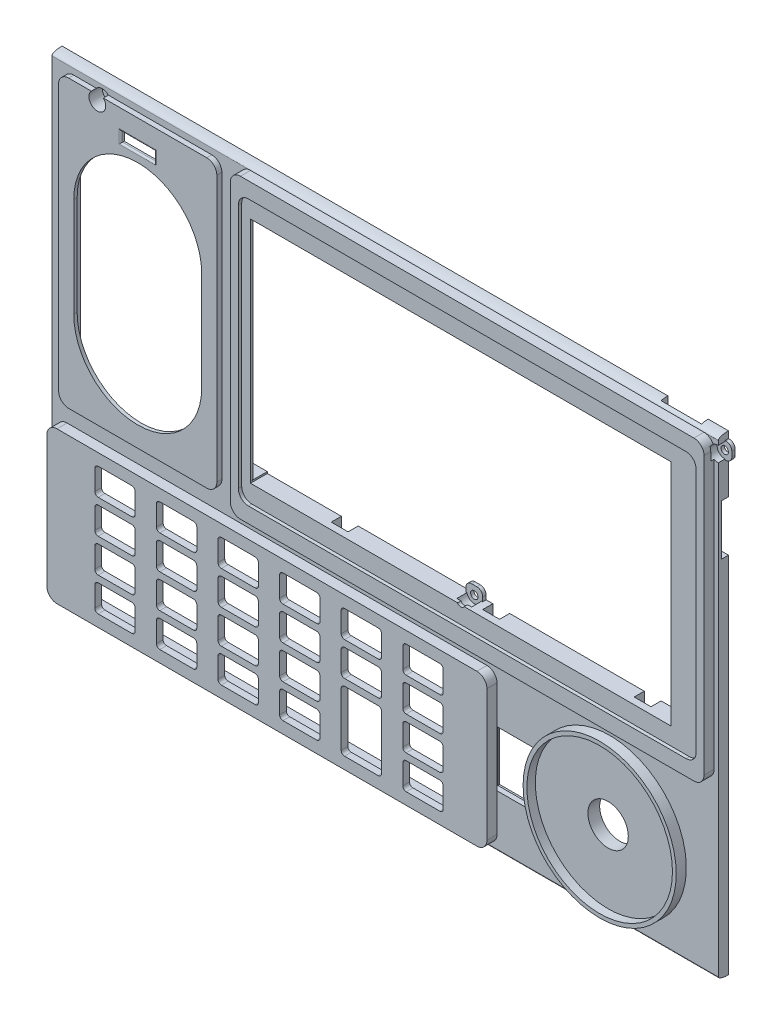
SolidWorks part; units mm, degrees
ref_plane "Front Plane" through (0, 0, 0) normal (0, 0, 1) x (1, 0, 0)
ref_plane "Top Plane" through (0, 0, 0) normal (0, 1, 0) x (1, 0, 0)
ref_plane "Right Plane" through (0, 0, 0) normal (1, 0, 0) x (0, 0, -1)
sketch "Sketch1" plane through (0, 0, 0) normal (0, 0, 1) x (1, 0, 0)
  line L1 (99, -70) -> (-99, -70)
  line L2 (99, -70) -> (99, 70)
  line L3 (99, 70) -> (-99, 70)
  line L4 (-99, -70) -> (-99, 70)
  line L5 (99, -70) -> (-99, 70) construction
  line L6 (99, 70) -> (-99, -70) construction
  point P0 (0, 0)
  dimension "D1" = 198
  dimension "D2" = 140
extrude "main_body" add sketch "Sketch1" along normal blind 3
fillet "long_corners" radius 3 2 edges at (0, 70, 3) (0, -70, 3) second distance 1 first distance on face at (0, 70, 1.5) first distance on face at (0, -70, 1.5)
sketch "Sketch2" plane through (0, 0, 3) normal (0, 0, 1) x (1, 0, 0)
  line L0 (-99, 24.75) -> (99, 24.75) construction
  line L1 (-99, 69) -> (-99, -69) construction
  line L2 (99, -69) -> (99, 69) construction
  line L3 (99, 69) -> (-99, 69) construction
  line L4 (-48.5, -17.75) -> (-95.5, -17.75)
  line L5 (-48.5, -17.75) -> (-48.5, 67.25)
  line L6 (-48.5, 67.25) -> (-95.5, 67.25)
  line L7 (-95.5, -17.75) -> (-95.5, 67.25)
  line L8 (-48.5, -17.75) -> (-95.5, 67.25) construction
  line L9 (-48.5, 67.25) -> (-95.5, -17.75) construction
  point P6 (-72, 24.75)
  dimension "D1" = 85
  dimension "D2" = 47
  dimension "D3" = 27
  dimension "D4" = 44.25
extrude "speaker" add sketch "Sketch2" along normal blind 1.5
fillet "speaker_corners" radius 3 4 edges at (-95.5, 67.25, 3.75) (-95.5, -17.75, 3.75) (-48.5, -17.75, 3.75) (-48.5, 67.25, 3.75)
sketch "Sketch19" plane through (0, 0, 4.5) normal (0, 0, 1) x (1, 0, 0)
  line L0 (-72, 67.25) -> (-72, -17.75) construction
  line L1 (-51.5, 67.25) -> (-92.5, 67.25) construction
  line L2 (-92.5, -17.75) -> (-51.5, -17.75) construction
  line L3 (-72, 7.25) -> (-72, 36.75) construction
  line L4 (-95.5, 64.25) -> (-95.5, -14.75) construction
  line L5 (-95.5, 24.75) -> (-48.5, 24.75) construction
  line L6 (-48.5, -14.75) -> (-48.5, 64.25) construction
  line L7 (-91, 7.25) -> (-91, 36.75)
  line L8 (-53, 7.25) -> (-53, 36.75)
  arc A0 (-91, 7.25) -> (-53, 7.25) centre (-72, 7.25) ccw
  arc A1 (-53, 36.75) -> (-91, 36.75) centre (-72, 36.75) ccw
  point P14 (-72, 22)
  point P19 (-72, -11.75)
  point P20 (-72, 55.75)
  dimension "D2" = 67.5
  dimension "D1" = 38
  dimension "D3" = 11.5
  dimension "D4" = 6
extrude "speaker_cut" cut sketch "Sketch19" against normal through all
sketch "Sketch21" plane through (0, 0, 0) normal (0, 0, -1) x (-1, 0, 0)
  line L0 (72, -11.75) -> (72, 55.75) construction
  line L2 (53, 7.25) -> (53, 36.75) construction
  line L3 (53, 22) -> (91, 22) construction
  line L4 (91, 36.75) -> (91, 7.25) construction
  line L5 (50.5, 61) -> (93.5, 61)
  line L6 (50.5, 61) -> (50.5, -17)
  line L7 (50.5, -17) -> (93.5, -17)
  line L8 (93.5, 61) -> (93.5, -17)
  line L9 (50.5, 61) -> (93.5, -17) construction
  line L10 (50.5, -17) -> (93.5, 61) construction
  arc A0 (53, 7.25) -> (91, 7.25) centre (72, 7.25) ccw construction
  arc A1 (91, 36.75) -> (53, 36.75) centre (72, 36.75) ccw construction
  point P14 (72, 22)
  dimension "D1" = 43
  dimension "D2" = 78
extrude "speaker_slot" cut sketch "Sketch21" against normal blind 3.5
sketch "Sketch3" plane through (0, 0, 3) normal (0, 0, 1) x (1, 0, 0)
  line L0 (-99, 24.875) -> (99, 24.875) construction
  line L1 (-99, 69) -> (-99, -69) construction
  line L2 (99, -69) -> (99, 69) construction
  line L4 (-48.5, -14.75) -> (-48.5, 64.25) construction
  line L5 (97.75, -19.25) -> (-43, -19.25)
  line L6 (97.75, -19.25) -> (97.75, 69)
  line L7 (97.75, 69) -> (-43, 69)
  line L8 (-43, -19.25) -> (-43, 69)
  line L9 (97.75, -19.25) -> (-43, 69) construction
  line L10 (97.75, 69) -> (-43, -19.25) construction
  line L11 (99, 70) -> (-99, 70) construction
  point P8 (27.375, 24.875)
  dimension "D1" = 1
  dimension "D2" = 88.25
  dimension "D3" = 140.75
  dimension "D4" = 1.25
  dimension "D5" = 5.5
extrude "lcd" add sketch "Sketch3" along normal blind 3
fillet "lcd_corners" radius 3 4 edges at (97.75, -19.25, 4.5) (-43, -19.25, 4.5)
sketch "Sketch9" plane through (0, 0, 6) normal (0, 0, 1) x (1, 0, 0)
  line L0 (-43, 24.85) -> (97.75, 24.85) construction
  line L1 (-43, 66) -> (-43, -16.25) construction
  line L2 (97.75, -16.25) -> (97.75, 66) construction
  line L3 (-40, -19.25) -> (94.75, -19.25) construction
  line L4 (95.4, -14.65) -> (-40.6, -14.65)
  line L5 (95.4, -14.65) -> (95.4, 64.35)
  line L6 (95.4, 64.35) -> (-40.6, 64.35)
  line L7 (-40.6, -14.65) -> (-40.6, 64.35)
  line L8 (95.4, -14.65) -> (-40.6, 64.35) construction
  line L9 (95.4, 64.35) -> (-40.6, -14.65) construction
  line L10 (94.75, 69) -> (-40, 69) construction
  line L11 (97.75, -16.25) -> (97.75, 66) construction
  point P6 (27.4, 24.85)
  dimension "D1" = 136
  dimension "D2" = 79
  dimension "D3" = 2.4
  dimension "D4" = 4.6
  dimension "D5" = 4.65
  dimension "D6" = 2.35
extrude "lcd_front" cut sketch "Sketch9" against normal blind 1
fillet "lcd_front_corners" radius 3 4 edges at (95.4, -14.65, 5.5) (95.4, 64.35, 5.5) (-40.6, 64.35, 5.5) (-40.6, -14.65, 5.5)
sketch "Sketch10" plane through (0, 0, 0) normal (0, 0, -1) x (-1, 0, 0)
  line L0 (-95.4, -11.65) -> (-95.4, 61.35) construction
  line L1 (-92.4, 64.35) -> (37.6, 64.35) construction
  line L2 (40.6, 64.35) -> (40.6, -14.65) construction
  line L3 (-95.4, 64.35) -> (40.6, 64.35) construction
  line L4 (38, -9.5) -> (-87, -9.5)
  line L5 (38, -9.5) -> (38, 58.5)
  line L6 (38, 58.5) -> (-87, 58.5)
  line L7 (-87, -9.5) -> (-87, 58.5)
  line L8 (-87, -9.5) -> (38, 58.5) construction
  line L9 (-87, 58.5) -> (38, -9.5) construction
  line L10 (-99, -70) -> (-99, 70) construction
  line L11 (-99, 70) -> (99, 70) construction
  line L13 (37.6, -14.65) -> (-92.4, -14.65) construction
  dimension "D1" = 125
  dimension "D2" = 68
  dimension "D3" = 12
  dimension "D4" = 2.6
  dimension "D5" = 11.5
  dimension "D6" = 5.85
  dimension "D7" = 8.4
  dimension "D8" = 5.85
  dimension "D9" = 5.15
extrude "lcd_back" cut sketch "Sketch10" against normal through all
sketch "Sketch56" plane through (0, 0, 0) normal (0, 0, -1) x (-1, 0, 0)
  line L0 (-87, -9.5) -> (38, -9.5) construction
  line L1 (-79, -9.5) -> (-74, -9.5)
  line L2 (-79, -9.5) -> (-79, -12.5)
  line L3 (-79, -12.5) -> (-74, -12.5)
  line L4 (-74, -9.5) -> (-74, -12.5)
  line L5 (38, 58.5) -> (-87, 58.5) construction
  line L6 (-34, -9.5) -> (-29, -9.5)
  line L7 (-34, -9.5) -> (-34, -12.5)
  line L8 (-34, -12.5) -> (-29, -12.5)
  line L9 (-29, -9.5) -> (-29, -12.5)
  line L10 (11, -9.5) -> (16, -9.5)
  line L11 (11, -9.5) -> (11, -12.5)
  line L12 (11, -12.5) -> (16, -12.5)
  line L13 (16, -9.5) -> (16, -12.5)
  line L14 (-79, 58.5) -> (-74, 58.5)
  line L15 (-79, 58.5) -> (-79, 61.5)
  line L16 (-79, 61.5) -> (-74, 61.5)
  line L17 (-74, 58.5) -> (-74, 61.5)
  line L18 (38, -9.5) -> (38, 58.5) construction
  line L19 (-34, 58.5) -> (-29, 58.5)
  line L20 (-34, 58.5) -> (-34, 61.5)
  line L21 (-34, 61.5) -> (-29, 61.5)
  line L22 (-29, 58.5) -> (-29, 61.5)
  line L23 (11, 58.5) -> (16, 58.5)
  line L24 (11, 58.5) -> (11, 61.5)
  line L25 (11, 61.5) -> (16, 61.5)
  line L26 (16, 58.5) -> (16, 61.5)
  line L27 (38, 58) -> (42, 58)
  line L28 (38, 58) -> (38, -9)
  line L29 (38, -9) -> (42, -9)
  line L30 (42, 58) -> (42, -9)
  line L31 (-99, -70) -> (-99, 70) construction
  line L32 (-99, 70) -> (99, 70) construction
  point P34 (-29, -11)
  dimension "D1" = 5
  dimension "D2" = 5
  dimension "D3" = 5
  dimension "D4" = 5
  dimension "D5" = 5
  dimension "D6" = 5
  dimension "D7" = 67
  dimension "D8" = 4
  dimension "D9" = 3
  dimension "D10" = 3
  dimension "D11" = 3
  dimension "D12" = 3
  dimension "D13" = 3
  dimension "D14" = 3
  dimension "D15" = 40
  dimension "D16" = 40
  dimension "D17" = 20
  dimension "D18" = 20
  dimension "D19" = 40
  dimension "D20" = 40
  dimension "D21" = 12
extrude "lcd_glue_points" cut sketch "Sketch56" against normal blind 3
sketch "Sketch4" plane through (0, 0, 3) normal (0, 0, 1) x (1, 0, 0)
  line L0 (-99, -45.75) -> (99, -45.75) construction
  line L1 (-99, 69) -> (-99, -69) construction
  line L2 (99, -69) -> (99, 69) construction
  line L4 (-92.5, -17.75) -> (-51.5, -17.75) construction
  line L5 (33.25, -68.25) -> (-97.5, -68.25)
  line L6 (33.25, -68.25) -> (33.25, -23.25)
  line L7 (33.25, -23.25) -> (-97.5, -23.25)
  line L8 (-97.5, -68.25) -> (-97.5, -23.25)
  line L9 (33.25, -68.25) -> (-97.5, -23.25) construction
  line L10 (33.25, -23.25) -> (-97.5, -68.25) construction
  line L11 (-99, -70) -> (99, -70) construction
  point P8 (-32.125, -45.75)
  dimension "D1" = 1.75
  dimension "D2" = 130.75
  dimension "D3" = 45
  dimension "D4" = 1.5
  dimension "D5" = 5.5
extrude "keypad" add sketch "Sketch4" along normal blind 3
fillet "keypad_corners" radius 3 4 edges at (-97.5, -68.25, 4.5) (33.25, -68.25, 4.5) (33.25, -23.25, 4.5) (-97.5, -23.25, 4.5)
sketch "Sketch25" plane through (0, 0, 6) normal (0, 0, 1) x (1, 0, 0)
  line L0 (-97.5, -30.75) -> (33.25, -30.75) construction
  line L1 (30.25, -23.25) -> (-94.5, -23.25) construction
  line L2 (-94.5, -68.25) -> (30.25, -68.25) construction
  line L3 (-77.25, -23.25) -> (-77.25, -68.25) construction
  line L5 (-34.65, -64.75) -> (33.25, -64.75) construction
  line L6 (-97.5, -26.25) -> (-97.5, -65.25) construction
  line L11 (33.25, -65.25) -> (33.25, -26.25) construction
  line L12 (-58.95, -23.25) -> (-58.95, -68.25) construction
  line L13 (-97.5, -40.75) -> (33.25, -40.75) construction
  line L14 (30.25, -23.25) -> (-94.5, -23.25) construction
  line L15 (-40.65, -23.25) -> (-40.65, -68.25) construction
  line L16 (-94.5, -68.25) -> (30.25, -68.25) construction
  line L17 (-71.25, -34.75) -> (-83.25, -34.75)
  line L18 (-22.35, -23.25) -> (-22.35, -68.25) construction
  line L19 (-97.5, -50.75) -> (33.25, -50.75) construction
  line L20 (-4.05, -23.25) -> (-4.05, -68.25) construction
  line L21 (-71.25, -34.75) -> (-71.25, -26.75)
  line L22 (14.25, -23.25) -> (14.25, -68.25) construction
  line L23 (-97.5, -26.25) -> (-97.5, -65.25) construction
  line L24 (-97.5, -60.75) -> (33.25, -60.75) construction
  line L25 (-71.25, -26.75) -> (-83.25, -26.75)
  line L26 (-83.25, -34.75) -> (-83.25, -26.75)
  line L27 (-71.25, -34.75) -> (-83.25, -26.75) construction
  line L28 (-71.25, -26.75) -> (-83.25, -34.75) construction
  line L29 (-71.25, -44.75) -> (-83.25, -44.75)
  line L30 (-71.25, -44.75) -> (-71.25, -36.75)
  line L31 (-71.25, -36.75) -> (-83.25, -36.75)
  line L32 (-83.25, -44.75) -> (-83.25, -36.75)
  line L33 (-71.25, -44.75) -> (-83.25, -36.75) construction
  line L34 (-71.25, -36.75) -> (-83.25, -44.75) construction
  line L35 (-71.25, -54.75) -> (-83.25, -54.75)
  line L36 (-71.25, -54.75) -> (-71.25, -46.75)
  line L37 (-71.25, -46.75) -> (-83.25, -46.75)
  line L38 (-83.25, -54.75) -> (-83.25, -46.75)
  line L39 (-71.25, -54.75) -> (-83.25, -46.75) construction
  line L40 (-71.25, -46.75) -> (-83.25, -54.75) construction
  line L41 (-71.25, -64.75) -> (-83.25, -64.75)
  line L42 (-71.25, -64.75) -> (-71.25, -56.75)
  line L43 (-71.25, -56.75) -> (-83.25, -56.75)
  line L44 (-83.25, -64.75) -> (-83.25, -56.75)
  line L45 (-71.25, -64.75) -> (-83.25, -56.75) construction
  line L46 (-71.25, -56.75) -> (-83.25, -64.75) construction
  line L47 (-52.95, -34.75) -> (-64.95, -34.75)
  line L48 (-52.95, -34.75) -> (-52.95, -26.75)
  line L49 (-52.95, -26.75) -> (-64.95, -26.75)
  line L50 (-64.95, -34.75) -> (-64.95, -26.75)
  line L51 (-52.95, -34.75) -> (-64.95, -26.75) construction
  line L52 (-52.95, -26.75) -> (-64.95, -34.75) construction
  line L53 (-52.95, -44.75) -> (-64.95, -44.75)
  line L54 (-52.95, -44.75) -> (-52.95, -36.75)
  line L55 (-52.95, -36.75) -> (-64.95, -36.75)
  line L56 (-64.95, -44.75) -> (-64.95, -36.75)
  line L57 (-52.95, -44.75) -> (-64.95, -36.75) construction
  line L58 (-52.95, -36.75) -> (-64.95, -44.75) construction
  line L59 (-52.95, -54.75) -> (-64.95, -54.75)
  line L60 (-52.95, -54.75) -> (-52.95, -46.75)
  line L61 (-52.95, -46.75) -> (-64.95, -46.75)
  line L62 (-64.95, -54.75) -> (-64.95, -46.75)
  line L63 (-52.95, -54.75) -> (-64.95, -46.75) construction
  line L64 (-52.95, -46.75) -> (-64.95, -54.75) construction
  line L65 (-52.95, -64.75) -> (-64.95, -64.75)
  line L66 (-52.95, -64.75) -> (-52.95, -56.75)
  line L67 (-52.95, -56.75) -> (-64.95, -56.75)
  line L68 (-64.95, -64.75) -> (-64.95, -56.75)
  line L69 (-52.95, -64.75) -> (-64.95, -56.75) construction
  line L70 (-52.95, -56.75) -> (-64.95, -64.75) construction
  line L71 (-34.65, -34.75) -> (-46.65, -34.75)
  line L72 (-34.65, -34.75) -> (-34.65, -26.75)
  line L73 (-34.65, -26.75) -> (-46.65, -26.75)
  line L74 (-46.65, -34.75) -> (-46.65, -26.75)
  line L75 (-34.65, -34.75) -> (-46.65, -26.75) construction
  line L76 (-34.65, -26.75) -> (-46.65, -34.75) construction
  line L77 (-34.65, -44.75) -> (-46.65, -44.75)
  line L78 (-34.65, -44.75) -> (-34.65, -36.75)
  line L79 (-34.65, -36.75) -> (-46.65, -36.75)
  line L80 (-46.65, -44.75) -> (-46.65, -36.75)
  line L81 (-34.65, -44.75) -> (-46.65, -36.75) construction
  line L82 (-34.65, -36.75) -> (-46.65, -44.75) construction
  line L83 (-34.65, -54.75) -> (-46.65, -54.75)
  line L84 (-34.65, -54.75) -> (-34.65, -46.75)
  line L85 (-34.65, -46.75) -> (-46.65, -46.75)
  line L86 (-46.65, -54.75) -> (-46.65, -46.75)
  line L87 (-34.65, -54.75) -> (-46.65, -46.75) construction
  line L88 (-34.65, -46.75) -> (-46.65, -54.75) construction
  line L89 (-34.65, -64.75) -> (-46.65, -64.75)
  line L90 (-34.65, -64.75) -> (-34.65, -56.75)
  line L91 (-34.65, -56.75) -> (-46.65, -56.75)
  line L92 (-46.65, -64.75) -> (-46.65, -56.75)
  line L93 (-34.65, -64.75) -> (-46.65, -56.75) construction
  line L94 (-34.65, -56.75) -> (-46.65, -64.75) construction
  line L95 (-16.35, -34.75) -> (-28.35, -34.75)
  line L96 (-16.35, -34.75) -> (-16.35, -26.75)
  line L97 (-16.35, -26.75) -> (-28.35, -26.75)
  line L98 (-28.35, -34.75) -> (-28.35, -26.75)
  line L99 (-16.35, -34.75) -> (-28.35, -26.75) construction
  line L100 (-16.35, -26.75) -> (-28.35, -34.75) construction
  line L101 (-16.35, -44.75) -> (-28.35, -44.75)
  line L102 (-16.35, -44.75) -> (-16.35, -36.75)
  line L103 (-16.35, -36.75) -> (-28.35, -36.75)
  line L104 (-28.35, -44.75) -> (-28.35, -36.75)
  line L105 (-16.35, -44.75) -> (-28.35, -36.75) construction
  line L106 (-16.35, -36.75) -> (-28.35, -44.75) construction
  line L111 (-16.35, -54.75) -> (-28.35, -54.75)
  line L112 (-16.35, -54.75) -> (-16.35, -46.75)
  line L113 (-16.35, -46.75) -> (-28.35, -46.75)
  line L114 (-28.35, -54.75) -> (-28.35, -46.75)
  line L115 (-16.35, -54.75) -> (-28.35, -46.75) construction
  line L116 (-16.35, -46.75) -> (-28.35, -54.75) construction
  line L117 (-16.35, -64.75) -> (-28.35, -64.75)
  line L118 (-16.35, -64.75) -> (-16.35, -56.75)
  line L119 (-16.35, -56.75) -> (-28.35, -56.75)
  line L120 (-28.35, -64.75) -> (-28.35, -56.75)
  line L121 (-16.35, -64.75) -> (-28.35, -56.75) construction
  line L122 (-16.35, -56.75) -> (-28.35, -64.75) construction
  line L127 (1.95, -34.75) -> (-10.05, -34.75)
  line L128 (1.95, -34.75) -> (1.95, -26.75)
  line L129 (1.95, -26.75) -> (-10.05, -26.75)
  line L130 (-10.05, -34.75) -> (-10.05, -26.75)
  line L131 (1.95, -34.75) -> (-10.05, -26.75) construction
  line L132 (1.95, -26.75) -> (-10.05, -34.75) construction
  line L133 (20.25, -34.75) -> (8.25, -34.75)
  line L134 (20.25, -34.75) -> (20.25, -26.75)
  line L135 (20.25, -26.75) -> (8.25, -26.75)
  line L136 (8.25, -34.75) -> (8.25, -26.75)
  line L137 (20.25, -34.75) -> (8.25, -26.75) construction
  line L138 (20.25, -26.75) -> (8.25, -34.75) construction
  line L139 (1.95, -44.75) -> (-10.05, -44.75)
  line L140 (1.95, -44.75) -> (1.95, -36.75)
  line L141 (1.95, -36.75) -> (-10.05, -36.75)
  line L142 (-10.05, -44.75) -> (-10.05, -36.75)
  line L143 (1.95, -44.75) -> (-10.05, -36.75) construction
  line L144 (1.95, -36.75) -> (-10.05, -44.75) construction
  line L145 (20.25, -44.75) -> (8.25, -44.75)
  line L146 (20.25, -44.75) -> (20.25, -36.75)
  line L147 (20.25, -36.75) -> (8.25, -36.75)
  line L148 (8.25, -44.75) -> (8.25, -36.75)
  line L149 (20.25, -44.75) -> (8.25, -36.75) construction
  line L150 (20.25, -36.75) -> (8.25, -44.75) construction
  line L151 (20.25, -54.75) -> (8.25, -54.75)
  line L152 (20.25, -54.75) -> (20.25, -46.75)
  line L153 (20.25, -46.75) -> (8.25, -46.75)
  line L154 (8.25, -54.75) -> (8.25, -46.75)
  line L155 (20.25, -54.75) -> (8.25, -46.75) construction
  line L156 (20.25, -46.75) -> (8.25, -54.75) construction
  line L157 (20.25, -64.75) -> (8.25, -64.75)
  line L158 (20.25, -64.75) -> (20.25, -56.75)
  line L159 (20.25, -56.75) -> (8.25, -56.75)
  line L160 (8.25, -64.75) -> (8.25, -56.75)
  line L161 (20.25, -64.75) -> (8.25, -56.75) construction
  line L162 (20.25, -56.75) -> (8.25, -64.75) construction
  line L163 (1.95, -64.75) -> (-10.05, -64.75)
  line L164 (1.95, -64.75) -> (1.95, -46.75)
  line L165 (1.95, -46.75) -> (-10.05, -46.75)
  line L166 (-10.05, -64.75) -> (-10.05, -46.75)
  line L167 (1.95, -64.75) -> (-10.05, -46.75) construction
  line L168 (1.95, -46.75) -> (-10.05, -64.75) construction
  point P34 (-77.25, -30.75)
  point P39 (-77.25, -40.75)
  point P44 (-77.25, -50.75)
  point P49 (-77.25, -60.75)
  point P54 (-58.95, -30.75)
  point P59 (-58.95, -40.75)
  point P64 (-58.95, -50.75)
  point P69 (-58.95, -60.75)
  point P74 (-40.65, -30.75)
  point P79 (-40.65, -40.75)
  point P84 (-40.65, -50.75)
  point P89 (-40.65, -60.75)
  point P94 (-22.35, -30.75)
  point P99 (-22.35, -40.75)
  point P104 (-22.35, -50.75)
  point P109 (-22.35, -60.75)
  point P114 (-4.05, -30.75)
  point P119 (14.25, -30.75)
  point P124 (-4.05, -40.75)
  point P129 (14.25, -40.75)
  point P134 (14.25, -50.75)
  point P139 (14.25, -60.75)
  point P144 (-4.05, -55.75)
  dimension "D1" = 19
  dimension "D2" = 18.3
  dimension "D3" = 18.3
  dimension "D4" = 18.3
  dimension "D5" = 18.3
  dimension "D6" = 18.3
  dimension "D7" = 20.25
  dimension "D8" = 7.5
  dimension "D9" = 10
  dimension "D10" = 10
  dimension "D11" = 10
  dimension "D12" = 7.5
  dimension "D13" = 12
  dimension "D14" = 12
  dimension "D15" = 12
  dimension "D16" = 12
  dimension "D17" = 12
  dimension "D18" = 12
  dimension "D19" = 12
  dimension "D20" = 12
  dimension "D21" = 12
  dimension "D22" = 12
  dimension "D23" = 12
  dimension "D24" = 12
  dimension "D25" = 12
  dimension "D26" = 12
  dimension "D27" = 12
  dimension "D28" = 12
  dimension "D29" = 12
  dimension "D30" = 12
  dimension "D31" = 12
  dimension "D32" = 12
  dimension "D33" = 12
  dimension "D34" = 12
  dimension "D35" = 12
  dimension "D36" = 8
  dimension "D37" = 8
  dimension "D38" = 8
  dimension "D39" = 8
  dimension "D40" = 8
  dimension "D41" = 8
  dimension "D42" = 18
  dimension "D43" = 8
  dimension "D44" = 8
  dimension "D45" = 8
  dimension "D46" = 8
  dimension "D47" = 8
  dimension "D48" = 8
  dimension "D49" = 8
  dimension "D50" = 8
  dimension "D51" = 8
  dimension "D52" = 8
  dimension "D53" = 8
  dimension "D54" = 8
  dimension "D55" = 8
  dimension "D56" = 8
  dimension "D57" = 8
  dimension "D58" = 8
  dimension "D59" = 5
extrude "keypad_cuts_0.8" cut sketch "Sketch25" against normal through all
sketch "Sketch5" plane through (0, 0, 3) normal (0, 0, 1) x (1, 0, 0)
  line L0 (33.25, -45.75) -> (99, -45.75) construction
  line L1 (33.25, -65.25) -> (33.25, -26.25) construction
  line L2 (99, -69) -> (99, 69) construction
  circle A0 centre (66.75, -45.75) radius 22.75
  dimension "D1" = 45.5
  dimension "D2" = 32.25
  dimension "D3" = 33.5
extrude "vfo" add sketch "Sketch5" along normal blind 3
sketch "Sketch7" plane through (0, 0, 6) normal (0, 0, 1) x (1, 0, 0)
  line L0 (44, -45.75) -> (89.5, -45.75) construction
  line L1 (66.75, -23) -> (66.75, -68.5) construction
  circle A0 centre (66.75, -45.75) radius 22.75 construction
  circle A1 centre (66.75, -45.75) radius 22.75 construction
  circle A2 centre (66.75, -45.75) radius 6
  dimension "D1" = 12
extrude "vfo_encoder_knob_cut" cut sketch "Sketch7" against normal through all
sketch "esp32" plane through (0, 0, 0) normal (0, 0, -1) x (-1, 0, 0)
  line L0 (99, -70) -> (-99, -70) construction
  line L1 (-50.5, -37.5) -> (-32, -37.5)
  line L2 (-50.5, -37.5) -> (-50.5, -54)
  line L3 (-50.5, -54) -> (-32, -54)
  line L4 (-32, -37.5) -> (-32, -54)
  line L5 (-99, -70) -> (-99, 70) construction
  dimension "D1" = 16
  dimension "D2" = 48.5
  dimension "D3" = 16.5
  dimension "D4" = 18.5
extrude "esp32_can_cut" cut sketch "esp32" against normal blind 3
sketch "Sketch47" plane through (0, 0, 0) normal (0, 0, -1) x (-1, 0, 0)
  line L0 (-50.5, -54) -> (-32, -54) construction
  line L1 (-31, -55) -> (-58, -55)
  line L2 (-31, -55) -> (-31, -36.5)
  line L3 (-31, -36.5) -> (-58, -36.5)
  line L4 (-58, -55) -> (-58, -36.5)
  line L5 (-31, -55) -> (-58, -36.5) construction
  line L6 (-31, -36.5) -> (-58, -55) construction
  line L7 (-50.5, -37.5) -> (-50.5, -54) construction
  point P0 (-44.5, -45.75)
  dimension "D1" = 27
  dimension "D2" = 18.5
  dimension "D3" = 1
  dimension "D4" = 7.5
extrude "esp32_ex_cut" cut sketch "Sketch47" against normal blind 1.5
sketch "Sketch49" plane through (0, 0, 0) normal (0, 0, -1) x (-1, 0, 0)
  line L0 (72, 59.75) -> (72, 67.25) construction
  line L3 (51.5, 67.25) -> (92.5, 67.25) construction
  line L4 (77, 58.25) -> (67, 58.25)
  line L5 (77, 58.25) -> (77, 61.25)
  line L6 (77, 61.25) -> (67, 61.25)
  line L7 (67, 58.25) -> (67, 61.25)
  line L8 (77, 58.25) -> (67, 61.25) construction
  line L9 (77, 61.25) -> (67, 58.25) construction
  point P6 (72, 59.75)
  dimension "D1" = 10
  dimension "D2" = 3
  dimension "D3" = 7.5
extrude "amb_sensor" cut sketch "Sketch49" against normal through all
fillet "amb_corners" radius 0.5 4 edges at (-67, 59.75, 4.5) (-72, 61.25, 4.5) (-77, 59.75, 4.5) (-72, 58.25, 4.5)
sketch "Sketch55" plane through (0, 0, 0) normal (0, 0, -1) x (-1, 0, 0)
  line L0 (-99, -70) -> (-99, 70) construction
  line L5 (-93, 70) -> (-81, 70)
  line L6 (-93, 70) -> (-93, 58.5)
  line L11 (-93, 58.5) -> (-81, 58.5)
  line L12 (-81, 70) -> (-81, 58.5)
  line L13 (94.5, 48) -> (99, 48)
  line L14 (94.5, 48) -> (94.5, 33)
  line L15 (94.5, 33) -> (99, 33)
  line L16 (99, 48) -> (99, 33)
  line L17 (94.5, 48) -> (99, 33) construction
  line L18 (94.5, 33) -> (99, 48) construction
  line L23 (99, 65.5) -> (-99, 65.5) construction
  line L24 (99, -8.5) -> (-99, -8.5) construction
  line L35 (-99, -68) -> (99, -68) construction
  line L36 (99, -70) -> (-99, -70) construction
  line L42 (-99, 53) -> (-93, 53)
  line L43 (-99, 53) -> (-99, 38)
  line L44 (-99, 70) -> (99, 70) construction
  line L45 (-99, 38) -> (-93, 38)
  line L46 (99, 70) -> (99, -70) construction
  line L47 (-93, 53) -> (-93, 38)
  circle A1 centre (49.5, 65.5) radius 3
  circle A2 centre (-24.5, 65.5) radius 3
  circle A4 centre (49.5, -8.5) radius 3
  circle A6 centre (-68, -68) radius 3
  circle A7 centre (-1, -68) radius 3
  circle A9 centre (-32, 65.5) radius 3
  point P10 (96.75, 40.5)
  dimension "D8" = 6
  dimension "D9" = 6
  dimension "D13" = 6
  dimension "D18" = 2
  dimension "D19" = 6
  dimension "D21" = 6
  dimension "D22" = 6
  dimension "D1" = 12
  dimension "D3" = 11.5
  dimension "D4" = 0
  dimension "D5" = 6
  dimension "D6" = 4.5
  dimension "D11" = 49.5
  dimension "D12" = 123.5
  dimension "D14" = 7.5
  dimension "D15" = 61.5
  dimension "D24" = 100
  dimension "D25" = 15
  dimension "D26" = 4.5
  dimension "D27" = 0
  dimension "D28" = 22
  dimension "D29" = 49.5
  dimension "D30" = 67
  dimension "D31" = 6
  dimension "D32" = 15
  dimension "D33" = 0
  dimension "D34" = 17
extrude "conn_cutouts" cut sketch "Sketch55" against normal blind 2
fillet "Fillet1" radius 2 1 edges at (-38, 24.5, 3)
fillet "Fillet2" radius 5 1 edges at (-42, 24.5, 0)
sketch "Sketch57" plane through (0, 0, 0) normal (0, 0, -1) x (-1, 0, 0)
  line L0 (99, 70) -> (99, 48) construction
  line L1 (-24, -24.5) -> (89, -24.5)
  line L2 (-24, -24.5) -> (-24, -66.5)
  line L3 (-24, -66.5) -> (89, -66.5)
  line L4 (89, -24.5) -> (89, -66.5)
  line L5 (99, -70) -> (1.2361, -70) construction
  dimension "D1" = 113
  dimension "D2" = 42
  dimension "D3" = 10
  dimension "D4" = 3.5
extrude "keyboard_back" cut sketch "Sketch57" against normal blind 4
sketch "Sketch58" plane through (0, -9.5, 0) normal (0, 1, 0) x (1, 0, 0)
  line L1 (27, -1) -> (22, -1)
  line L2 (27, -1) -> (27, 0)
  line L3 (27, 0) -> (22, 0)
  line L4 (22, -1) -> (22, 0)
  line L5 (27, -1) -> (22, 0) construction
  line L6 (27, 0) -> (22, -1) construction
  line L7 (29, -3) -> (29, 0) construction
  line L9 (29, 0) -> (-11, 0) construction
  point P0 (24.5, -0.5)
  dimension "D1" = 1
  dimension "D2" = 5
  dimension "D3" = 2
  dimension "D4" = 0
extrude "behind_lcd_screew_mount" add sketch "Sketch58" along normal blind 3
sketch "Sketch59" plane through (-99, 0, 0) normal (-1, 0, 0) x (0, 0, 1)
  line L0 (0, 70) -> (0, 48) construction
  line L1 (0, -66.5) -> (1, -66.5)
  line L2 (0, -66.5) -> (0, -69.5)
  line L3 (0, -69.5) -> (1, -69.5)
  line L4 (1, -66.5) -> (1, -69.5)
  dimension "D1" = 1
  dimension "D2" = 3
  dimension "D3" = 66.5
extrude "keyb_screw_mount" add sketch "Sketch59" along normal blind 1
sketch "Sketch60" plane through (99, 0, 0) normal (1, 0, 0) x (0, 0, -1)
  line L0 (0, -70) -> (0, 38) construction
  line L1 (0, 68) -> (-1, 68)
  line L2 (0, 68) -> (0, 63)
  line L3 (0, 63) -> (-1, 63)
  line L4 (-1, 68) -> (-1, 63)
  dimension "D1" = 63
  dimension "D2" = 5
  dimension "D3" = 1
extrude "right_corner_screw_mount" add sketch "Sketch60" along normal blind 2
sketch "Sketch61" plane through (0, 0, 0) normal (0, 0, -1) x (-1, 0, 0)
  line L0 (-99, 70) -> (-93, 70) construction
  line L1 (-99, 68) -> (-99, 70) construction
  line L2 (-99, -9) -> (99, -9) construction
  line L3 (99, 70) -> (99, 48) construction
  line L5 (-99, -70) -> (-99, 38) construction
  line L6 (99, 70) -> (99, 48) construction
  line L7 (-3.2361, -70) -> (-65.7639, -70) construction
  line L8 (99, -69.5) -> (99, -70) construction
  line L9 (99, -70) -> (1.2361, -70) construction
  line L10 (-81, 70) -> (99, 70) construction
  circle A0 centre (-98.9, 65.5) radius 1.1
  circle A1 centre (-24.5, -9) radius 1.1
  circle A2 centre (98, -68) radius 1.1
  circle A3 centre (84, 65.5) radius 1.1
  dimension "D1" = 2.2
  dimension "D6" = 2.2
  dimension "D9" = 2.2
  dimension "D10" = 2.2
  dimension "D2" = 4.5
  dimension "D3" = 0.1
  dimension "D4" = 61
  dimension "D5" = 123.5
  dimension "D7" = 1
  dimension "D8" = 2
  dimension "D11" = 15
  dimension "D12" = 4.5
extrude "ui_screws" cut sketch "Sketch61" against normal through all
sketch "Sketch62" plane through (0, 0, 6) normal (0, 0, 1) x (1, 0, 0)
  line L0 (97.8, 65.5) -> (100, 65.5) construction
  line L1 (-98, -66.9) -> (-98, -69.1) construction
  line L2 (98.9, 66.6) -> (98.9, 64.4) construction
  line L4 (-96.9, -68) -> (-99.1, -68) construction
  circle A0 centre (24.5, -9) radius 2.25
  arc A1 (99, 66.5954) -> (99, 64.4046) centre (98.9, 65.5) ccw construction
  arc A2 (99, 64.4046) -> (99, 66.5954) centre (98.9, 65.5) ccw construction
  circle A3 centre (98.9, 65.5) radius 2.25
  arc A4 (-97.5417, -69) -> (-99, -67.5417) centre (-98, -68) ccw construction
  arc A5 (-98.4583, -69) -> (-97.5417, -69) centre (-98, -68) ccw construction
  arc A6 (-99, -67.5417) -> (-99, -68.4583) centre (-98, -68) ccw construction
  circle A7 centre (-98, -68) radius 2.25
  dimension "D1" = 4.5
  dimension "D2" = 4.5
  dimension "D3" = 4.5
extrude "ui_screw_head" cut sketch "Sketch62" against normal blind 3 from offset 2 offset against normal yes
fillet "ui_screw_mount_corners" radius 1.75 6 edges at (-100, -66.5, 0.5) (-100, -69.5, 0.5) (101, 63, 0.5) (101, 68, 0.5) (22, -6.5, 0.5) (27, -6.5, 0.5)
sketch "Sketch63" plane through (0, 0, 6) normal (0, 0, 1) x (1, 0, 0)
  circle A0 centre (66.75, -45.75) radius 21.625
  dimension "D1" = 43.25
extrude "enc_knob_slot" cut sketch "Sketch63" against normal blind 2.5
sketch "Sketch64" plane through (0, 0, 4.5) normal (0, 0, 1) x (1, 0, 0)
  circle A0 centre (-84, 65.5) radius 2.5
  dimension "D1" = 5
extrude "on_speaker_ui_screw_head" cut sketch "Sketch64" against normal blind 4
fillet "Fillet3" radius 2 4 edges at (-89, -66.5, 2) (-89, -24.5, 2) (24, -66.5, 2) (24, -24.5, 2)
fillet "Fillet4" radius 1 92 edges at (-83.25, -34.75, 5) (-71.25, -34.75, 5) (-71.25, -26.75, 5) (-83.25, -26.75, 5) (8.25, -64.75, 5) (20.25, -64.75, 5) (20.25, -56.75, 5) (8.25, -56.75, 5) (20.25, -54.75, 5) (8.25, -54.75, 5) (8.25, -46.75, 5) (20.25, -46.75, 5) (8.25, -44.75, 5) (20.25, -44.75, 5) (8.25, -36.75, 5) (20.25, -36.75, 5) (8.25, -34.75, 5) (20.25, -34.75, 5) (20.25, -26.75, 5) (8.25, -26.75, 5) (-10.05, -64.75, 5) (1.95, -64.75, 5) (-10.05, -46.75, 5) (1.95, -46.75, 5) (-10.05, -36.75, 5) (-10.05, -44.75, 5) (1.95, -44.75, 5) (1.95, -36.75, 5) (-10.05, -34.75, 5) (1.95, -34.75, 5) (-10.05, -26.75, 5) (1.95, -26.75, 5) (-28.35, -56.75, 5) (-28.35, -64.75, 5) (-16.35, -64.75, 5) (-16.35, -56.75, 5) (-28.35, -46.75, 5) (-28.35, -54.75, 5) (-16.35, -54.75, 5) (-16.35, -46.75, 5) (-28.35, -44.75, 5) (-16.35, -44.75, 5) (-16.35, -36.75, 5) (-28.35, -36.75, 5) (-28.35, -34.75, 5) (-16.35, -34.75, 5) (-16.35, -26.75, 5) (-28.35, -26.75, 5) (-34.65, -64.75, 5) (-46.65, -64.75, 5) (-46.65, -56.75, 5) (-34.65, -56.75, 5) (-46.65, -46.75, 5) (-46.65, -54.75, 5) (-34.65, -54.75, 5) (-34.65, -46.75, 5) (-46.65, -36.75, 5) (-46.65, -44.75, 5) (-34.65, -44.75, 5) (-34.65, -36.75, 5) (-46.65, -26.75, 5) (-46.65, -34.75, 5) (-34.65, -34.75, 5) (-34.65, -26.75, 5) (-64.95, -56.75, 5) (-64.95, -64.75, 5) (-52.95, -64.75, 5) (-52.95, -56.75, 5) (-52.95, -54.75, 5) (-64.95, -54.75, 5) (-64.95, -46.75, 5) (-52.95, -46.75, 5) (-64.95, -44.75, 5) (-52.95, -44.75, 5) (-64.95, -36.75, 5) (-52.95, -36.75, 5) (-64.95, -34.75, 5) (-52.95, -34.75, 5) (-52.95, -26.75, 5) (-64.95, -26.75, 5) (-83.25, -64.75, 5) (-83.25, -56.75, 5) (-71.25, -64.75, 5) (-71.25, -56.75, 5) (-83.25, -54.75, 5) (-83.25, -46.75, 5) (-71.25, -54.75, 5) (-71.25, -46.75, 5) (-83.25, -36.75, 5) (-83.25, -44.75, 5) (-71.25, -44.75, 5) (-71.25, -36.75, 5)
